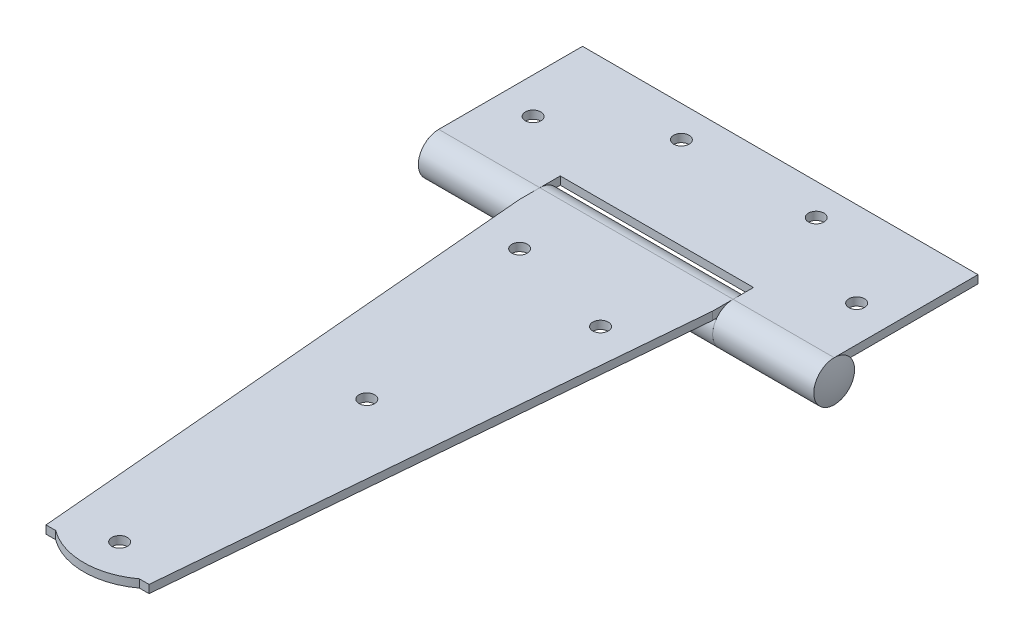
SolidWorks part; units mm, degrees
ref_plane "Front" through (0, 0, 0) normal (0, 0, 1) x (1, 0, 0)
ref_plane "Top" through (0, 0, 0) normal (0, 1, 0) x (1, 0, 0)
ref_plane "Right" through (0, 0, 0) normal (1, 0, 0) x (0, 0, -1)
sketch "Sketch1" plane through (0, 0, 0) normal (1, 0, 0) x (0, 0, -1)
  line L6 (0, 14.4272) -> (-195.2625, 14.4272)
  line L7 (-195.2625, 14.4272) -> (-195.2625, 11.5824)
  line L8 (-195.2625, 11.5824) -> (0, 11.5824)
  line L9 (0, 14.4272) -> (50.8, 14.4272)
  line L10 (50.8, 14.4272) -> (50.8, 11.5824)
  line L11 (50.8, 11.5824) -> (0, 11.5824)
  circle A0 centre (0, 7.2136) radius 7.2136
  circle A1 centre (0, 7.2136) radius 4.3656
  dimension "Pin Dia" = 8.7312
  dimension "knuckle dia" = 14.4272
  dimension "Th" = 2.8448
  dimension "A" = 195.2625
  dimension "C" = 50.8
sketch "Sketch2" plane through (0, 0, 0) normal (1, 0, 0) x (0, 0, -1)
  line L0 (0, 14.4272) -> (-195.2625, 14.4272)
  line L1 (-195.2625, 14.4272) -> (-195.2625, 11.5824)
  line L2 (-195.2625, 11.5824) -> (0, 11.5824)
  line L3 (-5.9249, 11.3284) -> (-3.5857, 9.7039)
  line L4 (0, 2.848) -> (0, 11.5824)
  arc A0 (0, 2.848) -> (-3.5857, 9.7039) centre (0, 7.2136) cw
  circle A1 centre (0, 7.2136) radius 7.2136 construction
  circle A3 centre (0, 7.2136) radius 4.3656 construction
  arc A4 (0, 14.4272) -> (-5.9249, 11.3284) centre (0, 7.2136) cw
  dimension "D1" = 0.254
extrude "Extrude1" add sketch "Sketch2" along normal mid plane 68.2625
sketch "Sketch4" plane through (0, 0, 0) normal (1, 0, 0) x (0, 0, -1)
  line L0 (0, 14.4272) -> (50.8, 14.4272)
  line L1 (50.8, 14.4272) -> (50.8, 11.5824)
  line L2 (50.8, 11.5824) -> (0, 11.5824)
  line L3 (0, 14.4272) -> (0, 0) construction
  line L4 (5.9249, 11.3284) -> (3.5857, 9.7039)
  line L5 (0, 11.5792) -> (0, 11.5824)
  arc A0 (0, 11.5792) -> (3.5857, 9.7039) centre (0, 7.2136) ccw
  arc A1 (-3.5857, 9.7039) -> (0, 2.848) centre (0, 7.2136) ccw construction
  circle A2 centre (0, 7.2136) radius 4.3656 construction
  arc A4 (0, 14.4272) -> (5.9249, 11.3284) centre (0, 7.2136) ccw
  circle A5 centre (0, 7.2136) radius 7.2136 construction
extrude "Extrude2" add sketch "Sketch4" along normal mid plane 139.7 separate body
sketch "Sketch6" plane through (0, 0, 0) normal (0, 1, 0) x (1, 0, 0)
  line L1 (-34.1313, -7.2136) -> (34.1313, -7.2136)
  line L2 (-34.1313, -7.2136) -> (-34.1313, 7.2136)
  line L3 (-34.1313, 7.2136) -> (34.1313, 7.2136)
  line L4 (34.1313, -7.2136) -> (34.1313, 7.2136)
extrude "Cut-Extrude3" cut sketch "Sketch6" along normal through all
ref_plane "Plane1" through (0, 7.2136, 0) normal (0, 1, 0) x (-1, 0, 0)
sketch "Sketch7" plane through (0, 7.2136, 0) normal (0, 1, 0) x (-1, 0, 0)
  line L0 (-71.0406, 0) -> (71.0406, 0)
  line L1 (-69.85, -7.2136) -> (-69.85, -4.3656)
  line L2 (-69.85, -4.3656) -> (69.85, -4.3656)
  line L3 (69.85, -4.3656) -> (69.85, -7.2136)
  line L4 (-69.85, 0) -> (-34.1313, 0) construction
  line L5 (69.85, -50.8) -> (69.85, 0) construction
  line L6 (-69.85, -50.8) -> (-69.85, 0) construction
  line L8 (-69.85, -7.2136) -> (-34.1313, -7.2136) construction
  line L9 (34.1313, -4.3656) -> (69.85, -4.3656) construction
  arc A0 (-71.0406, 0) -> (-69.85, -7.2136) centre (-48.5929, 0) ccw
  arc A1 (69.85, -7.2136) -> (71.0406, 0) centre (48.5929, 0) ccw
  dimension "D1" = 1.1906
revolve "Revolve1" add sketch "Sketch7" angle 360 about L0
sketch "Sketch8" plane through (0, 11.5824, 0) normal (0, -1, 0) x (1, 0, 0)
  line L0 (-18.2033, 190.3809) -> (-14.7902, 190.3809)
  line L1 (18.2033, 190.3809) -> (14.7902, 190.3809)
  line L2 (0, 195.2625) -> (0, 0) construction
  line L3 (34.1313, 7.2136) -> (73.025, 7.2136)
  line L4 (-34.1313, 7.2136) -> (-73.025, 7.2136)
  line L5 (-69.85, 0) -> (-69.85, -50.8) construction
  line L6 (34.1313, 195.2625) -> (-34.1313, 195.2625) construction
  line L9 (-18.2033, 190.3809) -> (18.2033, 190.3809) construction
  line L19 (-34.1313, 7.2136) -> (-18.2033, 190.3809)
  line L21 (73.025, 220.6625) -> (73.025, 7.2136)
  line L22 (-73.025, 220.6625) -> (73.025, 220.6625)
  line L23 (-73.025, 7.2136) -> (-73.025, 220.6625)
  line L24 (18.2033, 190.3809) -> (34.1313, 7.2136)
  arc A1 (-14.7902, 190.3809) -> (14.7902, 190.3809) centre (0, 170.416) cw
  point P0 (0, 195.2625)
  dimension "D1" = 3.4131
  dimension "D2" = 4.8816
  dimension "D3" = 3.175
  dimension "D4" = 25.4
  dimension "D5" = 36.4067
extrude "Cut-Extrude4" cut sketch "Sketch8" against normal blind 1056.132
sketch "a24 holes" plane through (0, 14.4272, 0) normal (0, -1, 0) x (1, 0, 0)
  line L0 (0, 0) -> (0, 73.9564) construction
  line L1 (57.15, -20.6375) -> (-57.15, -20.6375) construction
  circle A0 centre (0, 95.25) radius 2.7432
  circle A1 centre (-19.05, 22.225) radius 2.7432
  circle A2 centre (19.05, 31.75) radius 2.7432
  circle A3 centre (0, -39.6875) radius 2.7432
  circle A4 centre (57.15, -20.6375) radius 2.7432
  circle A5 centre (-57.15, -20.6375) radius 2.7432
  point P3 (0, -20.6375)
  dimension "hole size" = 5.4864
  dimension "8" = 19.05
  dimension "7" = 19.05
  dimension "6" = 63.5
  dimension "5" = 9.525
  dimension "3" = 20.6375
  dimension "2" = 114.3
  dimension "4" = 22.225
  dimension "1" = 39.6875
extrude "A24 hole cut" cut sketch "a24 holes" along normal through all
sketch "Sketch10" plane through (0, 14.4272, 0) normal (0, 1, 0) x (1, 0, 0)
  circle A0 centre (0, -182.5625) radius 2.7432
  circle A2 centre (0, -95.25) radius 2.7432 construction
  dimension "9" = 87.3125
extrude "Extrude3" cut sketch "Sketch10" against normal through all
sketch "Sketch11" plane through (0, 14.4272, 0) normal (0, 1, 0) x (1, 0, 0)
  circle A0 centre (0, -251.3896) radius 2.7432
  circle A1 centre (0, -95.25) radius 2.7432 construction
  circle A2 centre (0, -182.5625) radius 2.7432 construction
  dimension "10" = 68.8271
extrude "Extrude4" [suppressed] cut sketch "Sketch11" against normal through all
sketch "Sketch12" plane through (0, 14.4272, 0) normal (0, 1, 0) x (1, 0, 0)
  line L0 (-23.8125, 39.6875) -> (23.8125, 39.6875) construction
  circle A0 centre (-23.8125, 39.6875) radius 2.7432
  circle A1 centre (23.8125, 39.6875) radius 2.7432
  circle A2 centre (0, 39.6875) radius 2.7432 construction
  point P4 (0, 39.6875)
  dimension "11" = 47.625
extrude "Extrude5" cut sketch "Sketch12" against normal through all
other "DeleteFace1" face at (0, 14.4272, -42.4307) and patch yes
other "Move Face1" [suppressed] flip direction yes offset 9.525 parameters "D1"=9.525
other "Move Face2" [suppressed] offset 9.525 parameters "D1"=9.525
sketch "Sketch13" plane through (0, 14.4272, 0) normal (0, 1, 0) x (1, 0, 0)
  line L0 (57.15, 20.6375) -> (-57.15, 20.6375) construction
  circle A0 centre (0, 20.6375) radius 2.7432
  circle A1 centre (-57.15, 20.6375) radius 2.7432 construction
extrude "Extrude6" [suppressed] cut sketch "Sketch13" against normal through all
sketch "Sketch9" plane through (0, 0, 0) normal (0, 1, 0) x (1, 0, 0)
  line L0 (-69.85, 7.2136) -> (-69.85, -7.2136) construction
  line L1 (69.85, -7.2136) -> (69.85, 7.2136) construction
  point P0 (-69.85, 0)
  point P1 (69.85, 0)
equation "\"D1@Sketch8\" = \"D1@Extrude1\"*.05"
equation "\"D2@Sketch8\" = \"A@Sketch1\"*.025"
equation "\"D5@Sketch8\" = \"D1@Extrude1\"/1.875"
